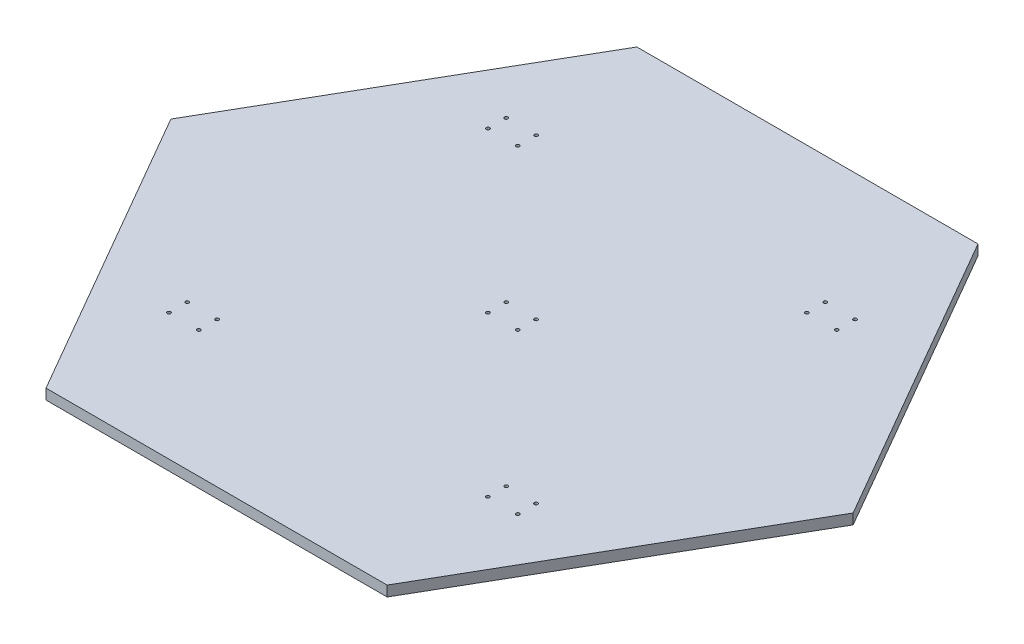
SolidWorks part; units mm, degrees
material "Pine"
ref_plane "Front Plane" through (0, 0, 0) normal (0, 0, 1) x (1, 0, 0)
ref_plane "Top Plane" through (0, 0, 0) normal (0, 1, 0) x (1, 0, 0)
ref_plane "Right Plane" through (0, 0, 0) normal (1, 0, 0) x (0, 0, -1)
sketch "Sketch1" plane through (0, 0, 0) normal (0, 1, 0) x (1, 0, 0)
  line L38 (835.3235, 0) -> (417.6617, 723.4114)
  line L39 (417.6617, 723.4114) -> (-417.6617, 723.4114)
  line L40 (-417.6617, 723.4114) -> (-835.3235, 0)
  line L41 (-835.3235, 0) -> (-417.6617, -723.4114)
  line L42 (-417.6617, -723.4114) -> (417.6617, -723.4114)
  line L43 (417.6617, -723.4114) -> (835.3235, 0)
  line L44 (762, 0) -> (381, 659.9114)
  line L45 (381, 659.9114) -> (-381, 659.9114)
  line L46 (-381, 659.9114) -> (-762, 0)
  line L47 (-762, 0) -> (-381, -659.9114)
  line L48 (-381, -659.9114) -> (381, -659.9114)
  line L49 (381, -659.9114) -> (762, 0)
  line L50 (762, 0) -> (381, 659.9114) construction
  line L51 (381, 659.9114) -> (-381, 659.9114) construction
  line L52 (-381, 659.9114) -> (-762, 0) construction
  line L53 (-762, 0) -> (-381, -659.9114) construction
  line L54 (-381, -659.9114) -> (381, -659.9114) construction
  line L55 (381, -659.9114) -> (762, 0) construction
  dimension "D1" = 0
  dimension "D2" = 63.5
extrude "Boss-Extrude1" add sketch "Sketch1" against normal blind 25.4
sketch "Sketch5" plane through (0, 0, 0) normal (0, -1, 0) x (-1, 0, 0)
  line L0 (-390.525, 390.525) -> (390.525, 390.525) construction
  line L1 (-427.101, 412.877) -> (-353.949, 412.877) construction
  line L2 (-427.101, 412.877) -> (-427.101, 368.173) construction
  line L3 (-427.101, 368.173) -> (-353.949, 368.173) construction
  line L4 (-353.949, 412.877) -> (-353.949, 368.173) construction
  line L5 (-390.525, 390.525) -> (-390.525, -390.525) construction
  line L6 (0, 390.525) -> (0, 0) construction
  line L9 (-355.6, 412.877) -> (-352.298, 412.877) construction
  line L10 (-355.6, 417.068) -> (-352.298, 417.068) construction
  line L11 (-355.6, 408.686) -> (-352.298, 408.686) construction
  line L12 (0, 0) -> (390.525, 0) construction
  line L15 (355.6, 412.877) -> (352.298, 412.877) construction
  line L18 (355.6, 417.068) -> (352.298, 417.068) construction
  line L19 (355.6, 408.686) -> (352.298, 408.686) construction
  line L20 (353.949, 412.877) -> (353.949, 368.173) construction
  line L22 (427.101, 368.173) -> (353.949, 368.173) construction
  line L23 (390.525, 390.525) -> (-390.525, 390.525)
  line L24 (390.525, -390.525) -> (390.525, 390.525)
  line L25 (-390.525, -390.525) -> (390.525, -390.525)
  line L31 (-390.525, 390.525) -> (-390.525, -390.525)
  line L34 (390.525, 390.525) -> (-390.525, 390.525) construction
  line L37 (390.525, -390.525) -> (390.525, 390.525) construction
  line L44 (-390.525, -390.525) -> (390.525, -390.525) construction
  line L47 (-390.525, 390.525) -> (-390.525, -390.525) construction
  line L48 (427.101, 412.877) -> (427.101, 368.173) construction
  line L49 (427.101, 412.877) -> (353.949, 412.877) construction
  line L50 (-355.6, -412.877) -> (-352.298, -412.877) construction
  line L51 (-355.6, -417.068) -> (-352.298, -417.068) construction
  line L52 (-355.6, -408.686) -> (-352.298, -408.686) construction
  line L53 (355.6, -412.877) -> (352.298, -412.877) construction
  line L54 (355.6, -417.068) -> (352.298, -417.068) construction
  line L55 (355.6, -408.686) -> (352.298, -408.686) construction
  line L56 (427.101, -412.877) -> (353.949, -412.877) construction
  line L57 (427.101, -412.877) -> (427.101, -368.173) construction
  line L58 (-390.525, 390.525) -> (-390.525, -390.525) construction
  line L59 (427.101, -368.173) -> (353.949, -368.173) construction
  line L60 (353.949, -412.877) -> (353.949, -368.173) construction
  line L61 (-353.949, -412.877) -> (-353.949, -368.173) construction
  line L62 (-427.101, -368.173) -> (-353.949, -368.173) construction
  line L63 (-427.101, -412.877) -> (-427.101, -368.173) construction
  line L64 (-427.101, -412.877) -> (-353.949, -412.877) construction
  arc A2 (-355.6, 417.068) -> (-355.6, 408.686) centre (-355.6, 412.877) ccw construction
  arc A3 (-352.298, 408.686) -> (-352.298, 417.068) centre (-352.298, 412.877) ccw construction
  circle A8 centre (-353.949, 412.877) radius 4.191
  circle A9 centre (-427.101, 412.877) radius 4.191
  circle A10 centre (-427.101, 368.173) radius 4.191
  circle A11 centre (-353.949, 368.173) radius 4.191
  arc A12 (355.6, 417.068) -> (355.6, 408.686) centre (355.6, 412.877) cw construction
  arc A13 (352.298, 408.686) -> (352.298, 417.068) centre (352.298, 412.877) cw construction
  circle A14 centre (353.949, 368.173) radius 4.191
  circle A15 centre (427.101, 368.173) radius 4.191
  circle A16 centre (427.101, 412.877) radius 4.191
  circle A17 centre (353.949, 412.877) radius 4.191
  arc A18 (-355.6, -417.068) -> (-355.6, -408.686) centre (-355.6, -412.877) cw construction
  arc A19 (-352.298, -408.686) -> (-352.298, -417.068) centre (-352.298, -412.877) cw construction
  arc A20 (355.6, -417.068) -> (355.6, -408.686) centre (355.6, -412.877) ccw construction
  arc A21 (352.298, -408.686) -> (352.298, -417.068) centre (352.298, -412.877) ccw construction
  circle A22 centre (353.949, -412.877) radius 4.191
  circle A23 centre (427.101, -412.877) radius 4.191
  circle A24 centre (427.101, -368.173) radius 4.191
  circle A25 centre (353.949, -368.173) radius 4.191
  circle A26 centre (-353.949, -368.173) radius 4.191
  circle A27 centre (-427.101, -368.173) radius 4.191
  circle A28 centre (-427.101, -412.877) radius 4.191
  circle A29 centre (-353.949, -412.877) radius 4.191
  point P4 (-390.525, 390.525)
  point P5 (-390.525, 412.877)
  point P6 (-353.949, 390.525)
  point P18 (-353.949, 412.877)
  point P27 (353.949, 412.877)
  point P45 (390.525, 390.525)
  point P48 (-353.949, -412.877)
  point P55 (353.949, -412.877)
  point P76 (390.525, -390.525)
  point P77 (-390.525, -390.525)
  dimension "D4" = 11.684
  dimension "D1" = 44.704
  dimension "D2" = 73.152
  dimension "D3" = 8.382
  dimension "D5" = 0
extrude "Cut-Extrude1" cut sketch "Sketch5" along normal up to surface (25.4 mm away) up to face at (0, -25.4, 0)
sketch "Sketch6" plane through (0, -25.4, 0) normal (0, -1, 0) x (-1, 0, 0)
  line L1 (-36.576, -22.352) -> (36.576, -22.352) construction
  line L2 (-36.576, -22.352) -> (-36.576, 22.352) construction
  line L3 (-36.576, 22.352) -> (36.576, 22.352) construction
  line L4 (36.576, -22.352) -> (36.576, 22.352) construction
  line L5 (-36.576, -22.352) -> (36.576, 22.352) construction
  line L6 (-36.576, 22.352) -> (36.576, -22.352) construction
  circle A0 centre (-36.576, 22.352) radius 4.191
  circle A1 centre (36.576, 22.352) radius 4.191
  circle A2 centre (36.576, -22.352) radius 4.191
  circle A3 centre (-36.576, -22.352) radius 4.191
  circle A4 centre (-353.949, 368.173) radius 4.191 construction
  point P0 (0, 0)
  dimension "D1" = 44.704
  dimension "D2" = 73.152
extrude "Cut-Extrude2" cut sketch "Sketch6" against normal up to surface (25.4 mm away) up to face at (-353.949, 0, 408.686)
